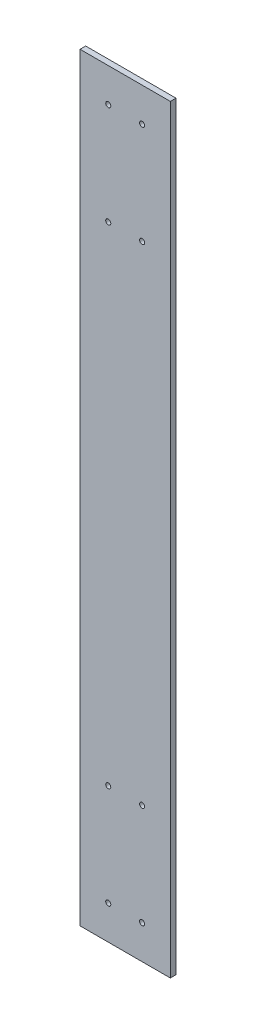
SolidWorks part; units mm, degrees
material "Acrylic (Medium-high impact)"
ref_plane "Front Plane" through (0, 0, 0) normal (0, 0, 1) x (1, 0, 0)
ref_plane "Top Plane" through (0, 0, 0) normal (0, 1, 0) x (1, 0, 0)
ref_plane "Right Plane" through (0, 0, 0) normal (1, 0, 0) x (0, 0, -1)
sketch "Sketch1" plane through (0, 0, 0) normal (0, 1, 0) x (1, 0, 0)
  line L0 (0, 0) -> (0, 76.2) construction
  line L2 (25.4, 68.667) -> (-25.4, 68.667)
  line L3 (25.4, 68.667) -> (25.4, 71.842)
  line L4 (25.4, 71.842) -> (-25.4, 71.842)
  line L5 (-25.4, 68.667) -> (-25.4, 71.842)
  line L6 (25.4, 68.667) -> (-25.4, 71.842) construction
  line L7 (25.4, 71.842) -> (-25.4, 68.667) construction
  circle A0 centre (0, 0) radius 76.2 construction
  point P4 (0, 70.2545)
  dimension "D1" = 152.4
  dimension "D2" = 3.175
  dimension "D3" = 50.8
extrude "Boss-Extrude1" add sketch "Sketch1" along normal blind 427.1518
sketch "Sketch2" plane through (0, 0, -68.667) normal (0, 0, 1) x (1, 0, 0)
  line L1 (-25.4, 427.1518) -> (25.4, 427.1518)
  line L2 (-25.4, 427.1518) -> (-25.4, 0)
  line L3 (-25.4, 0) -> (25.4, 0)
  line L4 (25.4, 427.1518) -> (25.4, 0)
sketch "Sketch3" plane through (0, 0, -68.667) normal (0, 0, 1) x (1, 0, 0)
  line L0 (0, 427.1518) -> (0, 0) construction
  line L1 (-25.4, 427.1518) -> (25.4, 427.1518) construction
  line L2 (-25.4, 0) -> (25.4, 0) construction
  line L3 (-25.4, 213.5759) -> (25.4, 213.5759) construction
  line L4 (-25.4, 427.1518) -> (-25.4, 0) construction
  line L5 (25.4, 427.1518) -> (25.4, 0) construction
  circle A0 centre (-19.05, 376.3518) radius 1.4224
  circle A1 centre (-12.7, 376.3518) radius 1.4224
  circle A2 centre (-6.35, 376.3518) radius 1.4224
  circle A3 centre (0, 376.3518) radius 1.4224
  circle A4 centre (6.35, 376.3518) radius 1.4224
  circle A5 centre (12.7, 376.3518) radius 1.4224
  circle A6 centre (19.05, 376.3518) radius 1.4224
  circle A7 centre (-12.7, 370.0018) radius 1.4224
  circle A8 centre (-6.35, 370.0018) radius 1.4224
  circle A9 centre (0, 370.0018) radius 1.4224
  circle A10 centre (6.35, 370.0018) radius 1.4224
  circle A11 centre (12.7, 370.0018) radius 1.4224
  circle A12 centre (19.05, 370.0018) radius 1.4224
  circle A13 centre (-12.7, 363.6518) radius 1.4224
  circle A14 centre (-6.35, 363.6518) radius 1.4224
  circle A15 centre (0, 363.6518) radius 1.4224
  circle A16 centre (6.35, 363.6518) radius 1.4224
  circle A17 centre (12.7, 363.6518) radius 1.4224
  circle A18 centre (19.05, 363.6518) radius 1.4224
  circle A19 centre (-12.7, 357.3018) radius 1.4224
  circle A20 centre (-6.35, 357.3018) radius 1.4224
  circle A21 centre (0, 357.3018) radius 1.4224
  circle A22 centre (6.35, 357.3018) radius 1.4224
  circle A23 centre (12.7, 357.3018) radius 1.4224
  circle A24 centre (19.05, 357.3018) radius 1.4224
  circle A25 centre (-12.7, 350.9518) radius 1.4224
  circle A26 centre (-6.35, 350.9518) radius 1.4224
  circle A27 centre (0, 350.9518) radius 1.4224
  circle A28 centre (6.35, 350.9518) radius 1.4224
  circle A29 centre (12.7, 350.9518) radius 1.4224
  circle A30 centre (19.05, 350.9518) radius 1.4224
  circle A31 centre (-12.7, 344.6018) radius 1.4224
  circle A32 centre (-6.35, 344.6018) radius 1.4224
  circle A33 centre (0, 344.6018) radius 1.4224
  circle A34 centre (6.35, 344.6018) radius 1.4224
  circle A35 centre (12.7, 344.6018) radius 1.4224
  circle A36 centre (19.05, 344.6018) radius 1.4224
  circle A37 centre (-12.7, 338.2518) radius 1.4224
  circle A38 centre (-6.35, 338.2518) radius 1.4224
  circle A39 centre (0, 338.2518) radius 1.4224
  circle A40 centre (6.35, 338.2518) radius 1.4224
  circle A41 centre (12.7, 338.2518) radius 1.4224
  circle A42 centre (19.05, 338.2518) radius 1.4224
  circle A43 centre (-12.7, 331.9018) radius 1.4224
  circle A44 centre (-6.35, 331.9018) radius 1.4224
  circle A45 centre (0, 331.9018) radius 1.4224
  circle A46 centre (6.35, 331.9018) radius 1.4224
  circle A47 centre (12.7, 331.9018) radius 1.4224
  circle A48 centre (19.05, 331.9018) radius 1.4224
  circle A49 centre (-19.05, 370.0018) radius 1.4224
  circle A50 centre (-19.05, 363.6518) radius 1.4224
  circle A51 centre (-19.05, 357.3018) radius 1.4224
  circle A52 centre (-19.05, 350.9518) radius 1.4224
  circle A53 centre (-19.05, 344.6018) radius 1.4224
  circle A54 centre (-19.05, 338.2518) radius 1.4224
  circle A55 centre (-19.05, 331.9018) radius 1.4224
  circle A56 centre (-19.05, 325.5518) radius 1.4224
  circle A57 centre (-12.7, 325.5518) radius 1.4224
  circle A58 centre (-6.35, 325.5518) radius 1.4224
  circle A59 centre (0, 325.5518) radius 1.4224
  circle A60 centre (6.35, 325.5518) radius 1.4224
  circle A61 centre (12.7, 325.5518) radius 1.4224
  circle A62 centre (19.05, 325.5518) radius 1.4224
  circle A63 centre (-19.05, 319.2018) radius 1.4224
  circle A64 centre (-12.7, 319.2018) radius 1.4224
  circle A65 centre (-6.35, 319.2018) radius 1.4224
  circle A66 centre (0, 319.2018) radius 1.4224
  circle A67 centre (6.35, 319.2018) radius 1.4224
  circle A68 centre (12.7, 319.2018) radius 1.4224
  circle A69 centre (19.05, 319.2018) radius 1.4224
  circle A70 centre (-19.05, 312.8518) radius 1.4224
  circle A71 centre (-12.7, 312.8518) radius 1.4224
  circle A72 centre (-6.35, 312.8518) radius 1.4224
  circle A73 centre (0, 312.8518) radius 1.4224
  circle A74 centre (6.35, 312.8518) radius 1.4224
  circle A75 centre (12.7, 312.8518) radius 1.4224
  circle A76 centre (19.05, 312.8518) radius 1.4224
  circle A77 centre (-19.05, 306.5018) radius 1.4224
  circle A78 centre (-12.7, 306.5018) radius 1.4224
  circle A79 centre (-6.35, 306.5018) radius 1.4224
  circle A80 centre (0, 306.5018) radius 1.4224
  circle A81 centre (6.35, 306.5018) radius 1.4224
  circle A82 centre (12.7, 306.5018) radius 1.4224
  circle A83 centre (19.05, 306.5018) radius 1.4224
  circle A84 centre (-19.05, 300.1518) radius 1.4224
  circle A85 centre (-12.7, 300.1518) radius 1.4224
  circle A86 centre (-6.35, 300.1518) radius 1.4224
  circle A87 centre (0, 300.1518) radius 1.4224
  circle A88 centre (6.35, 300.1518) radius 1.4224
  circle A89 centre (12.7, 300.1518) radius 1.4224
  circle A90 centre (19.05, 300.1518) radius 1.4224
  circle A91 centre (-19.05, 293.8018) radius 1.4224
  circle A92 centre (-12.7, 293.8018) radius 1.4224
  circle A93 centre (-6.35, 293.8018) radius 1.4224
  circle A94 centre (0, 293.8018) radius 1.4224
  circle A95 centre (6.35, 293.8018) radius 1.4224
  circle A96 centre (12.7, 293.8018) radius 1.4224
  circle A97 centre (19.05, 293.8018) radius 1.4224
  circle A98 centre (-19.05, 287.4518) radius 1.4224
  circle A99 centre (-12.7, 287.4518) radius 1.4224
  circle A100 centre (-6.35, 287.4518) radius 1.4224
  circle A101 centre (0, 287.4518) radius 1.4224
  circle A102 centre (6.35, 287.4518) radius 1.4224
  circle A103 centre (12.7, 287.4518) radius 1.4224
  circle A104 centre (19.05, 287.4518) radius 1.4224
  circle A105 centre (19.05, 139.7) radius 1.4224
  circle A106 centre (12.7, 139.7) radius 1.4224
  circle A107 centre (6.35, 139.7) radius 1.4224
  circle A108 centre (0, 139.7) radius 1.4224
  circle A109 centre (-6.35, 139.7) radius 1.4224
  circle A110 centre (-12.7, 139.7) radius 1.4224
  circle A111 centre (-19.05, 139.7) radius 1.4224
  circle A112 centre (19.05, 133.35) radius 1.4224
  circle A113 centre (12.7, 133.35) radius 1.4224
  circle A114 centre (6.35, 133.35) radius 1.4224
  circle A115 centre (0, 133.35) radius 1.4224
  circle A116 centre (-6.35, 133.35) radius 1.4224
  circle A117 centre (-12.7, 133.35) radius 1.4224
  circle A118 centre (-19.05, 133.35) radius 1.4224
  circle A119 centre (19.05, 127) radius 1.4224
  circle A120 centre (12.7, 127) radius 1.4224
  circle A121 centre (6.35, 127) radius 1.4224
  circle A122 centre (0, 127) radius 1.4224
  circle A123 centre (-6.35, 127) radius 1.4224
  circle A124 centre (-12.7, 127) radius 1.4224
  circle A125 centre (-19.05, 127) radius 1.4224
  circle A126 centre (19.05, 120.65) radius 1.4224
  circle A127 centre (12.7, 120.65) radius 1.4224
  circle A128 centre (6.35, 120.65) radius 1.4224
  circle A129 centre (0, 120.65) radius 1.4224
  circle A130 centre (-6.35, 120.65) radius 1.4224
  circle A131 centre (-12.7, 120.65) radius 1.4224
  circle A132 centre (-19.05, 120.65) radius 1.4224
  circle A133 centre (19.05, 114.3) radius 1.4224
  circle A134 centre (12.7, 114.3) radius 1.4224
  circle A135 centre (6.35, 114.3) radius 1.4224
  circle A136 centre (0, 114.3) radius 1.4224
  circle A137 centre (-6.35, 114.3) radius 1.4224
  circle A138 centre (-12.7, 114.3) radius 1.4224
  circle A139 centre (-19.05, 114.3) radius 1.4224
  circle A140 centre (19.05, 107.95) radius 1.4224
  circle A141 centre (12.7, 107.95) radius 1.4224
  circle A142 centre (6.35, 107.95) radius 1.4224
  circle A143 centre (0, 107.95) radius 1.4224
  circle A144 centre (-6.35, 107.95) radius 1.4224
  circle A145 centre (-12.7, 107.95) radius 1.4224
  circle A146 centre (-19.05, 107.95) radius 1.4224
  circle A147 centre (19.05, 101.6) radius 1.4224
  circle A148 centre (12.7, 101.6) radius 1.4224
  circle A149 centre (6.35, 101.6) radius 1.4224
  circle A150 centre (0, 101.6) radius 1.4224
  circle A151 centre (-6.35, 101.6) radius 1.4224
  circle A152 centre (-12.7, 101.6) radius 1.4224
  circle A153 centre (-19.05, 101.6) radius 1.4224
  circle A154 centre (-19.05, 95.25) radius 1.4224
  circle A155 centre (-19.05, 88.9) radius 1.4224
  circle A156 centre (-19.05, 82.55) radius 1.4224
  circle A157 centre (-19.05, 76.2) radius 1.4224
  circle A158 centre (-19.05, 69.85) radius 1.4224
  circle A159 centre (-19.05, 63.5) radius 1.4224
  circle A160 centre (-19.05, 57.15) radius 1.4224
  circle A161 centre (19.05, 95.25) radius 1.4224
  circle A162 centre (12.7, 95.25) radius 1.4224
  circle A163 centre (6.35, 95.25) radius 1.4224
  circle A164 centre (0, 95.25) radius 1.4224
  circle A165 centre (-6.35, 95.25) radius 1.4224
  circle A166 centre (-12.7, 95.25) radius 1.4224
  circle A167 centre (19.05, 88.9) radius 1.4224
  circle A168 centre (12.7, 88.9) radius 1.4224
  circle A169 centre (6.35, 88.9) radius 1.4224
  circle A170 centre (0, 88.9) radius 1.4224
  circle A171 centre (-6.35, 88.9) radius 1.4224
  circle A172 centre (-12.7, 88.9) radius 1.4224
  circle A173 centre (19.05, 82.55) radius 1.4224
  circle A174 centre (12.7, 82.55) radius 1.4224
  circle A175 centre (6.35, 82.55) radius 1.4224
  circle A176 centre (0, 82.55) radius 1.4224
  circle A177 centre (-6.35, 82.55) radius 1.4224
  circle A178 centre (-12.7, 82.55) radius 1.4224
  circle A179 centre (19.05, 76.2) radius 1.4224
  circle A180 centre (12.7, 76.2) radius 1.4224
  circle A181 centre (6.35, 76.2) radius 1.4224
  circle A182 centre (0, 76.2) radius 1.4224
  circle A183 centre (-6.35, 76.2) radius 1.4224
  circle A184 centre (-12.7, 76.2) radius 1.4224
  circle A185 centre (19.05, 69.85) radius 1.4224
  circle A186 centre (12.7, 69.85) radius 1.4224
  circle A187 centre (6.35, 69.85) radius 1.4224
  circle A188 centre (0, 69.85) radius 1.4224
  circle A189 centre (-6.35, 69.85) radius 1.4224
  circle A190 centre (-12.7, 69.85) radius 1.4224
  circle A191 centre (19.05, 63.5) radius 1.4224
  circle A192 centre (12.7, 63.5) radius 1.4224
  circle A193 centre (6.35, 63.5) radius 1.4224
  circle A194 centre (0, 63.5) radius 1.4224
  circle A195 centre (-6.35, 63.5) radius 1.4224
  circle A196 centre (-12.7, 63.5) radius 1.4224
  circle A197 centre (19.05, 57.15) radius 1.4224
  circle A198 centre (12.7, 57.15) radius 1.4224
  circle A199 centre (6.35, 57.15) radius 1.4224
  circle A200 centre (0, 57.15) radius 1.4224
  circle A201 centre (-6.35, 57.15) radius 1.4224
  circle A202 centre (-12.7, 57.15) radius 1.4224
  circle A203 centre (19.05, 50.8) radius 1.4224
  circle A204 centre (12.7, 50.8) radius 1.4224
  circle A205 centre (6.35, 50.8) radius 1.4224
  circle A206 centre (0, 50.8) radius 1.4224
  circle A207 centre (-6.35, 50.8) radius 1.4224
  circle A208 centre (-12.7, 50.8) radius 1.4224
  circle A209 centre (-19.05, 50.8) radius 1.4224
  dimension "D1" = 2.8448
  dimension "D2" = 6.35
  dimension "D3" = 50.8
  dimension "D4" = 7
  dimension "D5" = 8
  dimension "D6" = 8
sketch "Sketch4" plane through (0, 0, -68.667) normal (0, 0, 1) x (1, 0, 0)
  line L0 (0, 427.1518) -> (0, 0) construction
  line L1 (-25.4, 427.1518) -> (25.4, 427.1518) construction
  line L2 (-25.4, 0) -> (25.4, 0) construction
  circle A0 centre (-3.175, 376.3518) radius 1.4224
  circle A2 centre (-9.525, 376.3518) radius 1.4224
  circle A4 centre (-9.525, 370.0018) radius 1.4224
  circle A6 centre (-9.525, 363.6518) radius 1.4224
  circle A8 centre (-9.525, 357.3018) radius 1.4224
  circle A10 centre (-9.525, 350.9518) radius 1.4224
  circle A12 centre (-9.525, 344.6018) radius 1.4224
  circle A14 centre (-9.525, 338.2518) radius 1.4224
  circle A16 centre (-9.525, 331.9018) radius 1.4224
  circle A18 centre (-9.525, 325.5518) radius 1.4224
  circle A20 centre (-9.525, 319.2018) radius 1.4224
  circle A22 centre (-9.525, 312.8518) radius 1.4224
  circle A24 centre (-9.525, 306.5018) radius 1.4224
  circle A26 centre (-9.525, 300.1518) radius 1.4224
  circle A28 centre (-9.525, 293.8018) radius 1.4224
  circle A30 centre (-9.525, 287.4518) radius 1.4224
  circle A32 centre (-9.525, 281.1018) radius 1.4224
  circle A34 centre (-3.175, 370.0018) radius 1.4224
  circle A35 centre (-3.175, 363.6518) radius 1.4224
  circle A36 centre (-3.175, 357.3018) radius 1.4224
  circle A37 centre (-3.175, 350.9518) radius 1.4224
  circle A38 centre (-3.175, 344.6018) radius 1.4224
  circle A39 centre (-3.175, 338.2518) radius 1.4224
  circle A40 centre (-3.175, 331.9018) radius 1.4224
  circle A41 centre (-3.175, 325.5518) radius 1.4224
  circle A42 centre (-3.175, 319.2018) radius 1.4224
  circle A43 centre (-3.175, 312.8518) radius 1.4224
  circle A44 centre (-3.175, 306.5018) radius 1.4224
  circle A45 centre (-3.175, 300.1518) radius 1.4224
  circle A46 centre (-3.175, 293.8018) radius 1.4224
  circle A47 centre (-3.175, 287.4518) radius 1.4224
  circle A48 centre (-3.175, 281.1018) radius 1.4224
  circle A49 centre (3.175, 281.1018) radius 1.4224
  circle A50 centre (3.175, 287.4518) radius 1.4224
  circle A51 centre (3.175, 293.8018) radius 1.4224
  circle A52 centre (3.175, 300.1518) radius 1.4224
  circle A53 centre (3.175, 306.5018) radius 1.4224
  circle A54 centre (3.175, 312.8518) radius 1.4224
  circle A55 centre (3.175, 319.2018) radius 1.4224
  circle A56 centre (3.175, 325.5518) radius 1.4224
  circle A57 centre (3.175, 331.9018) radius 1.4224
  circle A58 centre (3.175, 338.2518) radius 1.4224
  circle A59 centre (3.175, 344.6018) radius 1.4224
  circle A60 centre (3.175, 350.9518) radius 1.4224
  circle A61 centre (3.175, 357.3018) radius 1.4224
  circle A62 centre (3.175, 363.6518) radius 1.4224
  circle A63 centre (3.175, 370.0018) radius 1.4224
  circle A65 centre (9.525, 281.1018) radius 1.4224
  circle A67 centre (9.525, 287.4518) radius 1.4224
  circle A69 centre (9.525, 293.8018) radius 1.4224
  circle A71 centre (9.525, 300.1518) radius 1.4224
  circle A73 centre (9.525, 306.5018) radius 1.4224
  circle A75 centre (9.525, 312.8518) radius 1.4224
  circle A77 centre (9.525, 319.2018) radius 1.4224
  circle A79 centre (9.525, 325.5518) radius 1.4224
  circle A81 centre (9.525, 331.9018) radius 1.4224
  circle A83 centre (9.525, 338.2518) radius 1.4224
  circle A85 centre (9.525, 344.6018) radius 1.4224
  circle A87 centre (9.525, 350.9518) radius 1.4224
  circle A89 centre (9.525, 357.3018) radius 1.4224
  circle A91 centre (9.525, 363.6518) radius 1.4224
  circle A93 centre (9.525, 370.0018) radius 1.4224
  circle A95 centre (9.525, 376.3518) radius 1.4224
  circle A96 centre (3.175, 376.3518) radius 1.4224
  circle A97 centre (-9.525, 382.7018) radius 1.4224
  circle A100 centre (9.525, 382.7018) radius 1.4224
  circle A103 centre (-9.525, 389.0518) radius 1.4224
  circle A106 centre (9.525, 389.0518) radius 1.4224
  circle A109 centre (-9.525, 395.4018) radius 1.4224
  circle A112 centre (9.525, 395.4018) radius 1.4224
  circle A115 centre (-9.525, 401.7518) radius 1.4224
  circle A118 centre (9.525, 401.7518) radius 1.4224
  circle A121 centre (-9.525, 408.1018) radius 1.4224
  circle A124 centre (9.525, 408.1018) radius 1.4224
  circle A127 centre (-9.525, 414.4518) radius 1.4224
  circle A130 centre (9.525, 414.4518) radius 1.4224
  circle A144 centre (-3.175, 382.7018) radius 1.4224 [skipped]
  circle A145 centre (-3.175, 389.0518) radius 1.4224 [skipped]
  circle A146 centre (-3.175, 395.4018) radius 1.4224 [skipped]
  circle A147 centre (-3.175, 401.7518) radius 1.4224 [skipped]
  circle A148 centre (-3.175, 408.1018) radius 1.4224 [skipped]
  circle A149 centre (-3.175, 414.4518) radius 1.4224 [skipped]
  circle A150 centre (3.175, 382.7018) radius 1.4224 [skipped]
  circle A151 centre (3.175, 389.0518) radius 1.4224 [skipped]
  circle A152 centre (3.175, 395.4018) radius 1.4224 [skipped]
  circle A153 centre (3.175, 401.7518) radius 1.4224 [skipped]
  circle A154 centre (3.175, 408.1018) radius 1.4224 [skipped]
  circle A155 centre (3.175, 414.4518) radius 1.4224 [skipped]
  circle A156 centre (-15.875, 363.6518) radius 1.4224 [skipped]
  circle A157 centre (-15.875, 357.3018) radius 1.4224 [skipped]
  circle A158 centre (-15.875, 350.9518) radius 1.4224 [skipped]
  circle A159 centre (-15.875, 344.6018) radius 1.4224 [skipped]
  circle A160 centre (-15.875, 338.2518) radius 1.4224 [skipped]
  circle A161 centre (-15.875, 331.9018) radius 1.4224 [skipped]
  circle A162 centre (-15.875, 325.5518) radius 1.4224 [skipped]
  circle A163 centre (-15.875, 319.2018) radius 1.4224 [skipped]
  circle A164 centre (-15.875, 312.8518) radius 1.4224 [skipped]
  circle A165 centre (-15.875, 306.5018) radius 1.4224 [skipped]
  circle A166 centre (-15.875, 300.1518) radius 1.4224 [skipped]
  circle A167 centre (-15.875, 293.8018) radius 1.4224 [skipped]
  circle A168 centre (-15.875, 287.4518) radius 1.4224 [skipped]
  circle A169 centre (-15.875, 281.1018) radius 1.4224 [skipped]
  circle A170 centre (-15.875, 376.3518) radius 1.4224 [skipped]
  circle A171 centre (-15.875, 370.0018) radius 1.4224 [skipped]
  dimension "D2" = 2.8448
  dimension "D1" = 3.175
  dimension "D3" = 50.8
  dimension "D4" = 3
  dimension "D5" = 16
  dimension "D7" = 7
extrude "Cut-Extrude2" cut sketch "Sketch4" against normal blind 5.08
sketch "Sketch5" plane through (0, 0, -68.667) normal (0, 0, 1) x (1, 0, 0)
  line L1 (-6.4666, 378.8778) -> (6.1161, 378.8778)
  line L2 (-6.4666, 378.8778) -> (-6.4666, 277.848)
  line L3 (-6.4666, 277.848) -> (6.1161, 277.848)
  line L4 (6.1161, 378.8778) -> (6.1161, 277.848)
extrude "Boss-Extrude2" add sketch "Sketch5" against normal blind 3.175
sketch "Sketch6" plane through (0, 0, -68.667) normal (0, 0, 1) x (1, 0, 0)
  line L1 (-20.2574, 381.0412) -> (-12.7108, 381.0412)
  line L2 (-20.2574, 381.0412) -> (-20.2574, 272.3701)
  line L3 (-20.2574, 272.3701) -> (-12.7108, 272.3701)
  line L4 (-12.7108, 381.0412) -> (-12.7108, 272.3701)
  line L5 (12.4446, 381.0412) -> (21.5005, 381.0412)
  line L6 (12.4446, 381.0412) -> (12.4446, 272.3701)
  line L7 (12.4446, 272.3701) -> (21.5005, 272.3701)
  line L8 (21.5005, 381.0412) -> (21.5005, 272.3701)
extrude "Boss-Extrude3" add sketch "Sketch6" against normal blind 3.175
sketch "Sketch7" plane through (0, 0, -68.667) normal (0, 0, 1) x (1, 0, 0)
  line L0 (25.4, 427.1518) -> (25.4, 0) construction
  line L1 (-25.4, 427.1518) -> (25.4, 427.1518)
  line L2 (-25.4, 427.1518) -> (-25.4, 410.6418)
  line L3 (-25.4, 410.6418) -> (25.4, 410.6418)
  line L4 (25.4, 427.1518) -> (25.4, 410.6418)
  dimension "D1" = 16.51
extrude "Boss-Extrude4" add sketch "Sketch7" against normal blind 3.175
sketch "Sketch8" plane through (0, 0, -68.667) normal (0, 0, 1) x (1, 0, 0)
  line L0 (-25.4, 427.1518) -> (-25.4, 0) construction
  line L1 (-25.4, 404.9269) -> (25.4, 404.9269)
  line L2 (-25.4, 404.9269) -> (-25.4, 353.7389)
  line L3 (-25.4, 353.7389) -> (25.4, 353.7389)
  line L4 (25.4, 404.9269) -> (25.4, 353.7389)
  line L5 (25.4, 427.1518) -> (25.4, 0) construction
extrude "Boss-Extrude5" add sketch "Sketch8" against normal blind 3.175
sketch "Sketch9" plane through (0, 0, -68.667) normal (0, 0, 1) x (1, 0, 0)
  line L0 (-25.4, 427.1518) -> (-25.4, 0) construction
  line L1 (-25.4, 347.6) -> (25.4, 347.6)
  line L2 (-25.4, 347.6) -> (-25.4, 277.4309)
  line L3 (-25.4, 277.4309) -> (25.4, 277.4309)
  line L4 (25.4, 347.6) -> (25.4, 277.4309)
  line L5 (25.4, 427.1518) -> (25.4, 0) construction
extrude "Boss-Extrude6" add sketch "Sketch9" against normal blind 3.175
sketch "Sketch10" plane through (0, 0, -68.667) normal (0, 0, 1) x (1, 0, 0)
  line L0 (-25.4, 213.5759) -> (25.4, 213.5759) construction
  line L1 (-25.4, 427.1518) -> (-25.4, 0) construction
  line L2 (25.4, 427.1518) -> (25.4, 0) construction
ref_plane "Plane1" through (0, 213.5759, 0) normal (0, 1, 0) x (1, 0, 0)
mirror "Mirror1" about plane through (0, 213.5759, 0) normal (0, 1, 0) of "Boss-Extrude4", "Boss-Extrude6", "Boss-Extrude5", "Boss-Extrude3", "Boss-Extrude2", "Cut-Extrude2"
